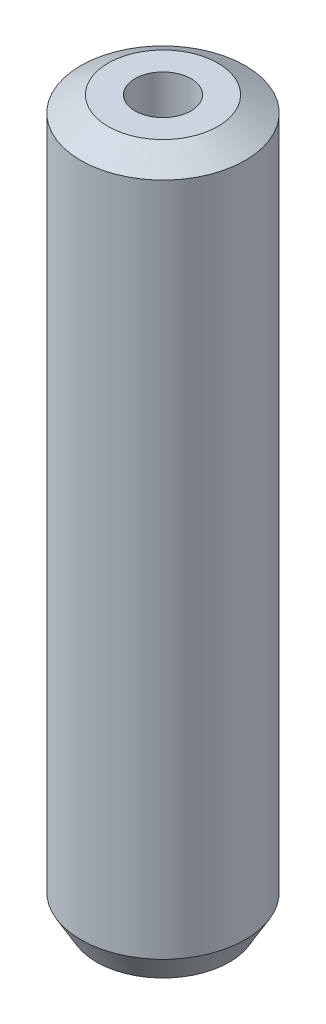
SolidWorks part; units mm, degrees
ref_plane "Front Plane" through (0, 0, 0) normal (0, 0, 1) x (1, 0, 0)
ref_plane "Top Plane" through (0, 0, 0) normal (0, 1, 0) x (1, 0, 0)
ref_plane "Right Plane" through (0, 0, 0) normal (1, 0, 0) x (0, 0, -1)
sketch "Sketch1" plane through (0, 0, 0) normal (0, 1, 0) x (1, 0, 0)
  circle A0 centre (0, 0) radius 15
  dimension "SHAFT_OD" = 30
extrude "Boss-Extrude1" add sketch "Sketch1" along normal blind 130.9901
sketch "Sketch2" plane through (0, 0, 0) normal (0, 1, 0) x (1, 0, 0)
  circle A0 centre (0, 0) radius 5.1086
  dimension "BORE_D" = 10.2171
extrude "Cut-Extrude1" cut sketch "Sketch2" along normal through all
chamfer "Chamfer1" distance 2.8796 angle 60 2 edges at (0, 130.9901, 15) (0, 0, 15) first distance on face at (0, 130.9901, 15) first distance on face at (0, 0, 5.1086)
